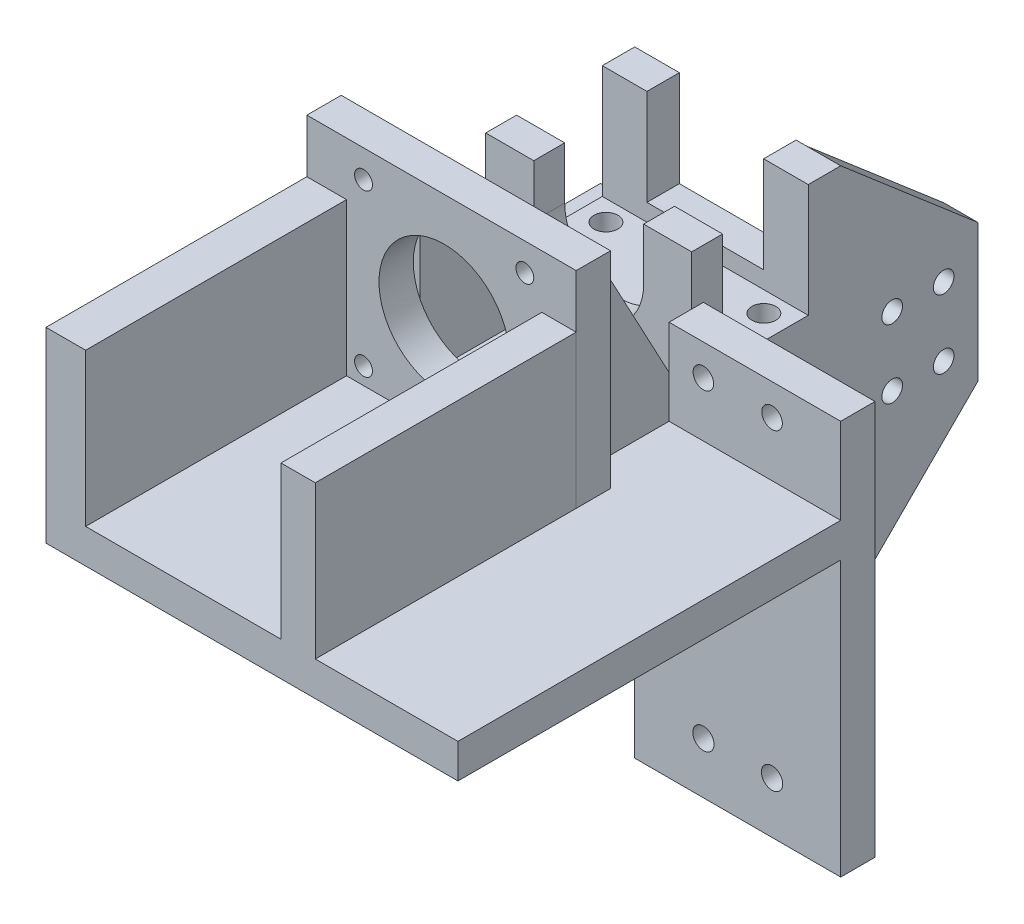
SolidWorks part; units mm, degrees
ref_plane "Front Plane" through (0, 0, 0) normal (0, 0, 1) x (1, 0, 0)
ref_plane "Top Plane" through (0, 0, 0) normal (0, 1, 0) x (1, 0, 0)
ref_plane "Right Plane" through (0, 0, 0) normal (1, 0, 0) x (0, 0, -1)
sketch "Sketch1" plane through (0, 0, 0) normal (0, 1, 0) x (1, 0, 0)
  line L0 (0, 0) -> (0, 161.51)
  line L1 (0, 161.51) -> (60, 161.51)
  line L2 (60, 161.51) -> (60, 121.51)
  line L3 (60, 121.51) -> (110, 121.51)
  line L4 (110, 121.51) -> (110, 0)
  line L5 (110, 0) -> (0, 0)
  dimension "D1" = 161.51
  dimension "D2" = 60
  dimension "D3" = 50
  dimension "D4" = 121.51
extrude "Boss-Extrude1" add sketch "Sketch1" along normal blind 10
sketch "Sketch2" plane through (0, 10, 0) normal (0, 1, 0) x (1, 0, 0)
  line L0 (0, 161.51) -> (0, 0) construction
  line L1 (0, 152.1) -> (60, 152.1)
  line L2 (0, 152.1) -> (0, 127.1)
  line L3 (0, 127.1) -> (60, 127.1)
  line L4 (60, 152.1) -> (60, 127.1)
  line L5 (60, 121.51) -> (60, 161.51) construction
  line L6 (60, 161.51) -> (0, 161.51) construction
  dimension "D1" = 9.41
  dimension "D2" = 25
extrude "Boss-Extrude2" add sketch "Sketch2" along normal blind 6.45
sketch "Sketch3" plane through (0, 10, 0) normal (0, 1, 0) x (1, 0, 0)
  line L0 (60, 152.1) -> (60, 161.51) construction
  line L1 (0, 161.51) -> (60, 161.51)
  line L2 (0, 161.51) -> (0, 152.06)
  line L3 (0, 152.06) -> (60, 152.06)
  line L4 (60, 161.51) -> (60, 152.06)
  dimension "D1" = 9.45
extrude "Boss-Extrude3" add sketch "Sketch3" along normal blind 39.45
sketch "Sketch4" plane through (0, 0, -161.51) normal (0, 0, -1) x (-1, 0, 0)
  line L0 (-60, 49.45) -> (0, 49.45) construction
  line L1 (-47, 49.45) -> (-13, 49.45)
  line L2 (-47, 49.45) -> (-47, 21.45)
  line L3 (-47, 21.45) -> (-13, 21.45)
  line L4 (-13, 49.45) -> (-13, 21.45)
  line L5 (-60, 49.45) -> (-60, 0) construction
  line L6 (0, 49.45) -> (0, 0) construction
  dimension "D1" = 13
  dimension "D2" = 13
  dimension "D3" = 28
extrude "Cut-Extrude1" cut sketch "Sketch4" against normal blind 9.45
sketch "Sketch5" plane through (0, 10, 0) normal (0, 1, 0) x (1, 0, 0)
  line L0 (60, 127.1) -> (60, 152.06) construction
  line L1 (0, 127.1) -> (60, 127.1)
  line L2 (0, 127.1) -> (0, 118.1)
  line L3 (0, 118.1) -> (60, 118.1)
  line L4 (60, 127.1) -> (60, 118.1)
  dimension "D1" = 9
extrude "Boss-Extrude4" add sketch "Sketch5" along normal blind 39.45
sketch "Sketch6" plane through (0, 0, -118.1) normal (0, 0, 1) x (1, 0, 0)
  line L0 (30, 49.45) -> (30, 10) construction
  line L1 (0, 49.45) -> (60, 49.45) construction
  line L2 (0, 10) -> (60, 10) construction
  line L3 (14, 34.24) -> (14, 49.45)
  line L4 (14, 49.45) -> (46, 49.45)
  line L5 (46, 49.45) -> (46, 34.24)
  arc A0 (14, 34.24) -> (46, 34.24) centre (30, 34.24) ccw
  dimension "D1" = 16
  dimension "D2" = 15.21
extrude "Cut-Extrude2" cut sketch "Sketch6" against normal up to next
sketch "Sketch7" plane through (0, 0, 0) normal (0, -1, 0) x (1, 0, 0)
  line L0 (110, -111.51) -> (50, -111.51)
  line L1 (110, 0) -> (110, -121.51) construction
  line L2 (50, -111.51) -> (50, -161.51)
  line L3 (60, -161.51) -> (0, -161.51) construction
  line L4 (50, -161.51) -> (60, -161.51)
  line L5 (60, -161.51) -> (60, -121.51)
  line L6 (60, -121.51) -> (110, -121.51)
  line L7 (110, -121.51) -> (110, -111.51)
  dimension "D1" = 10
  dimension "D2" = 10
extrude "Boss-Extrude5" add sketch "Sketch7" along normal blind 80
sketch "Sketch8" plane through (0, 0, 0) normal (-1, 0, 0) x (0, 0, 1)
  line L0 (-161.51, 0) -> (0, 0) construction
  line L1 (-75.9971, 0) -> (0, 0)
  line L2 (-75.9971, 0) -> (-75.9971, 54.4584)
  line L3 (-75.9971, 54.4584) -> (0, 54.4584)
  line L4 (0, 0) -> (0, 54.4584)
  line L5 (0, 10) -> (0, 0) construction
  dimension "D1" = 75.9971
extrude "Boss-Extrude6" add sketch "Sketch8" along normal blind 10
sketch "Sketch9" plane through (0, 10, 0) normal (0, 1, 0) x (1, 0, 0)
  line L0 (0, 0) -> (110, 0) construction
  line L1 (58.45, 75.9971) -> (68.45, 75.9971)
  line L2 (58.45, 75.9971) -> (58.45, 0)
  line L3 (58.45, 0) -> (68.45, 0)
  line L4 (68.45, 75.9971) -> (68.45, 0)
  line L5 (0, 0) -> (0, 75.9971) construction
  line L6 (-10, 75.9971) -> (0, 75.9971) construction
  dimension "D1" = 58.45
  dimension "D2" = 10
extrude "Boss-Extrude7" add sketch "Sketch9" along normal blind 44.46
sketch "Sketch17" plane through (0, 10, 0) normal (0, 1, 0) x (1, 0, 0)
  line L0 (0, 0) -> (58.45, 0) construction
  line L1 (68.45, 86) -> (-10, 86)
  line L2 (68.45, 86) -> (68.45, 76)
  line L3 (68.45, 76) -> (-10, 76)
  line L4 (-10, 86) -> (-10, 76)
  line L5 (-10, 0) -> (-10, 75.9971) construction
  dimension "D1" = 78.45
  dimension "D2" = 10
  dimension "D3" = 76
  dimension "D4" = 78.45
extrude "Boss-Extrude27" add sketch "Sketch17" along normal blind 60
sketch "Sketch19" plane through (0, 0, -86) normal (0, 0, -1) x (-1, 0, 0)
  line L0 (0, 10) -> (10, 10) construction
  line L1 (0, 70) -> (-2.5, 70)
  line L2 (0, 70) -> (0, 10)
  line L3 (0, 10) -> (-2.5, 10)
  line L4 (-2.5, 70) -> (-2.5, 10)
  line L5 (10, 70) -> (10, 10) construction
  line L6 (-68.45, 70) -> (10, 70) construction
  line L7 (-13, 70) -> (-10.5, 70)
  line L8 (-13, 70) -> (-13, 10)
  line L9 (-13, 10) -> (-10.5, 10)
  line L10 (-10.5, 70) -> (-10.5, 10)
  line L12 (-47, 70) -> (-49.5, 70)
  line L13 (-47, 70) -> (-47, 10)
  line L14 (-47, 10) -> (-49.5, 10)
  line L15 (-49.5, 70) -> (-49.5, 10)
  line L16 (-57.5, 70) -> (-60, 70)
  line L17 (-57.5, 70) -> (-57.5, 10)
  line L18 (-57.5, 10) -> (-60, 10)
  line L19 (-60, 70) -> (-60, 10)
  dimension "D1" = 10
  dimension "D2" = 2.5
  dimension "D3" = 60
  dimension "D4" = 8
  dimension "D5" = 2.5
  dimension "D6" = 60
  dimension "D7" = 2.5
  dimension "D8" = 8
  dimension "D9" = 2.5
  dimension "D10" = 60
  dimension "D11" = 60
  dimension "D12" = 34
extrude "Boss-Extrude31" add sketch "Sketch19" along normal blind 32
sketch "Sketch20" plane through (0, 0, 0) normal (1, 0, 0) x (0, 0, -1)
  line L1 (0, 54.4584) -> (75.9971, 54.4584)
  line L2 (0, 54.4584) -> (0, 10)
  line L3 (0, 10) -> (75.9971, 10)
  line L4 (75.9971, 54.4584) -> (75.9971, 10)
extrude "Boss-Extrude32" add sketch "Sketch20" along normal blind 1.55
sketch "Sketch21" plane through (0, 0, -76) normal (0, 0, 1) x (1, 0, 0)
  line L0 (-10, 70) -> (-10, 10) construction
  line L1 (-10, 70) -> (68.45, 70) construction
  line L2 (53.5, 61.95) -> (6.5, 14.95) construction
  line L3 (53.5, 14.95) -> (6.5, 61.95) construction
  circle A0 centre (6.5, 61.95) radius 2.6
  circle A1 centre (53.5, 61.95) radius 2.6
  circle A2 centre (53.5, 14.95) radius 2.6
  circle A3 centre (6.5, 14.95) radius 2.6
  circle A4 centre (30, 38.45) radius 19
  dimension "D5" = 5.2
  dimension "D6" = 38
  dimension "D1" = 16.5
  dimension "D2" = 8.05
  dimension "D3" = 47
  dimension "D4" = 47
extrude "Cut-Extrude3" cut sketch "Sketch21" against normal blind 10
sketch "Sketch22" plane through (0, 0, 0) normal (0, -1, 0) x (1, 0, 0)
  line L0 (50, -161.51) -> (0, -161.51) construction
  line L1 (0, -161.51) -> (0, -75.9971) construction
  circle A0 centre (7.02, -146.1) radius 3.5
  circle A1 centre (7.02, -133) radius 3.5
  circle A2 centre (53.02, -146.1) radius 3.5
  circle A3 centre (53.02, -133) radius 3.5
  dimension "D4" = 7
  dimension "D1" = 13.1
  dimension "D2" = 15.41
  dimension "D3" = 7.02
  dimension "D5" = 46
extrude "Cut-Extrude4" cut sketch "Sketch22" against normal up to next
sketch "Sketch23" plane through (50, 0, 0) normal (-1, 0, 0) x (0, 0, 1)
  line L0 (-147.8691, 0) -> (-161.51, 0) construction
  line L1 (-153.1, 0) -> (-126.1, 0)
  line L2 (-153.1, 0) -> (-153.1, -6)
  line L3 (-153.1, -6) -> (-126.1, -6)
  line L4 (-126.1, 0) -> (-126.1, -6)
  line L10 (-161.51, -80) -> (-161.51, 0) construction
  dimension "D1" = 27
  dimension "D2" = 8.41
  dimension "D3" = 6
extrude "Cut-Extrude5" cut sketch "Sketch23" against normal up to next
sketch "Sketch24" plane through (50, 0, 0) normal (-1, 0, 0) x (0, 0, 1)
  line L0 (-161.51, -80) -> (-161.51, 0) construction
  line L1 (-111.51, -80) -> (-111.51, 0) construction
  line L2 (-111.51, -80) -> (-161.51, -80) construction
  circle A0 centre (-151.51, -15) radius 3.1
  circle A1 centre (-151.51, -65) radius 3.1
  circle A2 centre (-131.51, -15) radius 3.1
  circle A3 centre (-131.51, -65) radius 3.1
  dimension "D5" = 6.2
  dimension "D1" = 10
  dimension "D2" = 20
  dimension "D3" = 15
  dimension "D4" = 50
extrude "Cut-Extrude6" cut sketch "Sketch24" against normal up to next
sketch "Sketch25" plane through (0, 0, -111.51) normal (0, 0, 1) x (1, 0, 0)
  line L0 (50, -80) -> (50, 0) construction
  line L1 (110, -80) -> (50, -80) construction
  circle A0 centre (70, -15) radius 3.1
  circle A1 centre (90, -15) radius 3.1
  circle A2 centre (70, -65) radius 3.1
  circle A3 centre (90, -65) radius 3.1
  dimension "D5" = 6.2
  dimension "D1" = 20
  dimension "D2" = 20
  dimension "D3" = 15
  dimension "D4" = 50
extrude "Cut-Extrude7" cut sketch "Sketch25" against normal up to next
sketch "Sketch26" plane through (0, 0, 0) normal (-1, 0, 0) x (0, 0, 1)
  line L2 (-118.1, 10) -> (-86, 70)
  line L3 (-86, 70) -> (-118, 70)
  line L4 (-118, 70) -> (-118.1, 10)
extrude "Cut-Extrude10" cut sketch "Sketch26" against normal blind 70
sketch "Sketch27" plane through (0, 10, 0) normal (0, 1, 0) x (1, 0, 0)
  line L0 (60, 118) -> (60, 86) construction
  line L1 (110, 121.51) -> (60, 121.51)
  line L2 (110, 121.51) -> (110, 111.51)
  line L3 (110, 111.51) -> (60, 111.51)
  line L4 (60, 121.51) -> (60, 111.51)
  dimension "D1" = 10
extrude "Boss-Extrude33" add sketch "Sketch27" along normal blind 25
sketch "Sketch28" plane through (0, 0, -111.51) normal (0, 0, 1) x (1, 0, 0)
  line L0 (110, 35) -> (110, 10) construction
  line L1 (60, 35) -> (110, 35) construction
  circle A0 centre (90, 25.935) radius 3
  circle A1 centre (70, 25.935) radius 3
  dimension "D1" = 6
  dimension "D2" = 20
  dimension "D3" = 20
  dimension "D4" = 9.065
extrude "Cut-Extrude11" cut sketch "Sketch28" against normal up to next
sketch "Sketch29" plane through (0, 0, -161.51) normal (0, 0, -1) x (-1, 0, 0)
  line L0 (-60, 49.45) -> (-60, -80) construction
  line L1 (-60, 15.15) -> (-50, 15.15)
  line L2 (-60, 15.15) -> (-60, -24.85)
  line L3 (-60, -24.85) -> (-50, -24.85)
  line L4 (-50, 15.15) -> (-50, -24.85)
  line L5 (-50, -80) -> (-50, 0) construction
  line L6 (-60, 49.45) -> (-47, 49.45) construction
  dimension "D1" = 40
  dimension "D2" = 34.3
extrude "Boss-Extrude34" add sketch "Sketch29" along normal blind 40
sketch "Sketch30" plane through (50, 0, 0) normal (-1, 0, 0) x (0, 0, 1)
  line L0 (-201.51, 15.15) -> (-161.51, 15.15) construction
  line L1 (-201.51, -24.85) -> (-161.51, -24.85) construction
  line L2 (-201.51, -24.85) -> (-201.51, 15.15) construction
  circle A0 centre (-191.51, 5.15) radius 3
  circle A1 centre (-176.51, 5.15) radius 3
  circle A2 centre (-191.51, -14.85) radius 3
  circle A3 centre (-176.51, -14.85) radius 3
  dimension "D1" = 6
  dimension "D2" = 10
  dimension "D3" = 10
  dimension "D4" = 10
  dimension "D5" = 15
extrude "Cut-Extrude12" cut sketch "Sketch30" against normal up to next
sketch "Sketch31" plane through (50, 0, 0) normal (-1, 0, 0) x (0, 0, 1)
  line L0 (-161.51, 15.15) -> (-161.51, 49.45)
  line L1 (-161.51, 49.45) -> (-201.51, 15.15)
  line L2 (-201.51, 15.15) -> (-161.51, 15.15)
  line L3 (-161.51, -24.85) -> (-201.51, -24.85)
  line L4 (-201.51, -24.85) -> (-161.51, -64.85)
  line L5 (-161.51, -80) -> (-161.51, -24.85) construction
  line L6 (-161.51, -64.85) -> (-161.51, -24.85)
  dimension "D1" = 45
extrude "Boss-Extrude35" add sketch "Sketch31" against normal blind 10
sketch "Sketch34" plane through (0, 0, 0) normal (-1, 0, 0) x (0, 0, 1)
  line L1 (-76, 10) -> (-161.51, 10)
  line L2 (-76, 10) -> (-76, 0)
  line L3 (-76, 0) -> (-161.51, 0)
  line L4 (-161.51, 10) -> (-161.51, 0)
extrude "Boss-Extrude37" add sketch "Sketch34" along normal blind 10
